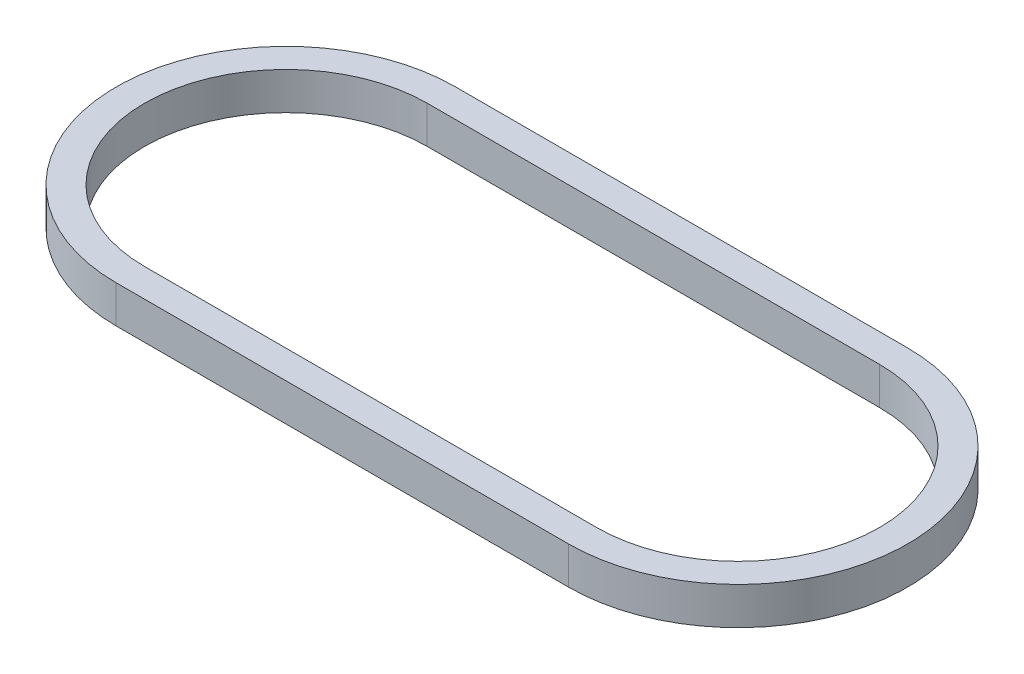
SolidWorks part; units mm, degrees
material "6061 Alloy"
ref_plane "Front Plane" through (0, 0, 0) normal (0, 0, 1) x (1, 0, 0)
ref_plane "Top Plane" through (0, 0, 0) normal (0, 1, 0) x (1, 0, 0)
ref_plane "Right Plane" through (0, 0, 0) normal (1, 0, 0) x (0, 0, -1)
sketch "Sketch1" plane through (0, 0, 0) normal (0, 1, 0) x (1, 0, 0)
  line L0 (-47.1, 0) -> (47.1, 0) construction
  line L1 (-47.1, 0) -> (47.1, 0) construction
  line L3 (-47.1, -35.3387) -> (47.1, -35.3387)
  line L4 (-47.1, 0) -> (47.1, 0) construction
  line L6 (-47.1, -29.4459) -> (47.1, -29.4459)
  line L7 (-47.1, 29.4459) -> (-47.1, 35.3387) construction
  line L8 (0, 0) -> (0, 18) construction
  line L9 (-47.1, 35.3387) -> (47.1, 35.3387)
  line L14 (-47.1, 29.4459) -> (47.1, 29.4459)
  arc A0 (-47.1, 35.3387) -> (-47.1, -35.3387) centre (-47.1, 0) ccw
  arc A1 (47.1, -35.3387) -> (47.1, 35.3387) centre (47.1, 0) ccw
  arc A2 (-47.1, 29.4459) -> (-47.1, -29.4459) centre (-47.1, 0) ccw
  arc A3 (47.1, -29.4459) -> (47.1, 29.4459) centre (47.1, 0) ccw
  point P0 (0, 0)
  point P4 (0, 0)
  point P10 (0, 0)
  point P11 (-47.1, 35.0286)
  point P12 (0, 0)
  point P13 (0, 0)
  point P17 (0, 0)
  point P18 (-47.1, 32.3923)
  point P19 (0, 0)
  point P20 (-47.1, 29.3607)
  point P21 (-47.1, 32.3923)
  dimension "D2" = 32.3923
  dimension "D3" = 5.8928
  dimension "D1" = 94.2
  dimension "D5" = 18
extrude "Boss-Extrude1" add sketch "Sketch1" along normal blind 7.7978 contours A0 L3 A1 A3 L6 A2 region at (-80.6448, 0, 0)
